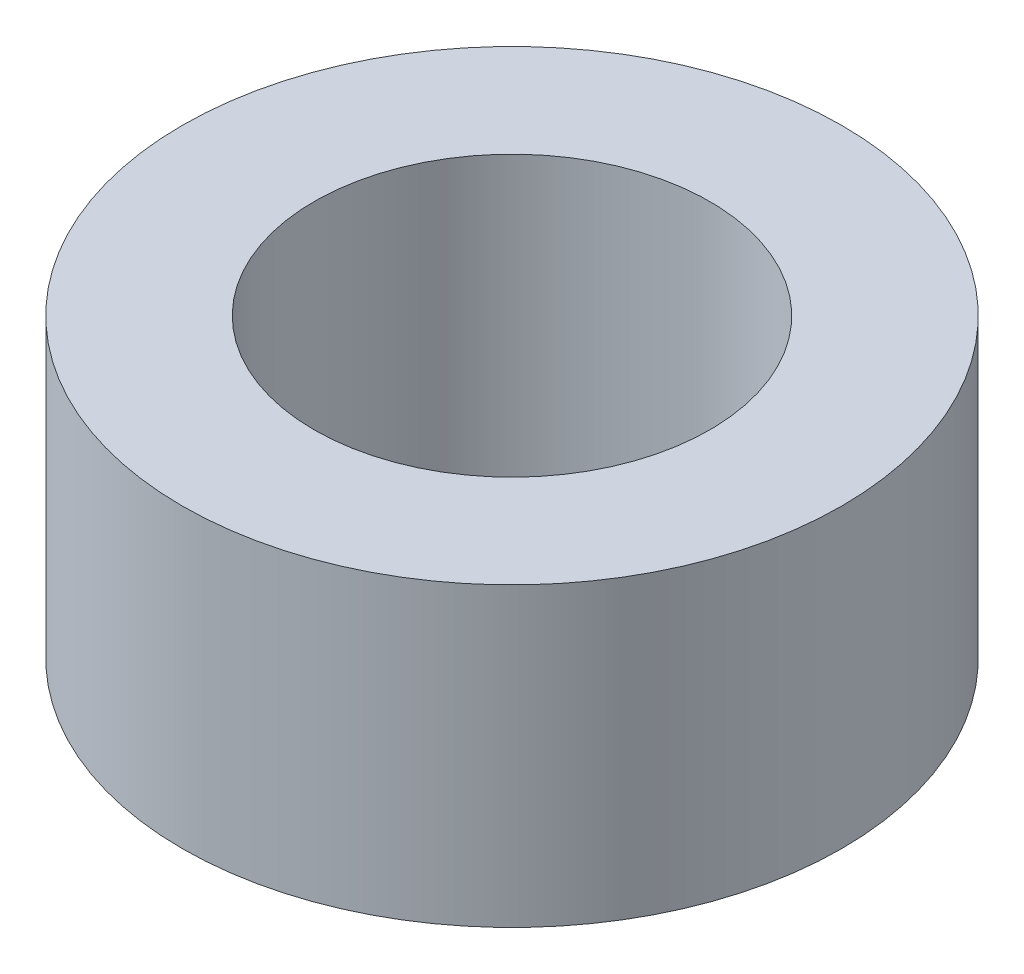
SolidWorks part; units mm, degrees
ref_plane "Front Plane" through (0, 0, 0) normal (0, 0, 1) x (1, 0, 0)
ref_plane "Top Plane" through (0, 0, 0) normal (0, 1, 0) x (1, 0, 0)
ref_plane "Right Plane" through (0, 0, 0) normal (1, 0, 0) x (0, 0, -1)
sketch "Sketch1" plane through (0, 0, 0) normal (0, 1, 0) x (1, 0, 0)
  circle A0 centre (0, 0) radius 7.9375
  circle A1 centre (0, 0) radius 4.7625
  dimension "D1" = 9.525
  dimension "D2" = 15.875
extrude "Boss-Extrude1" add sketch "Sketch1" along normal blind 7.1437
